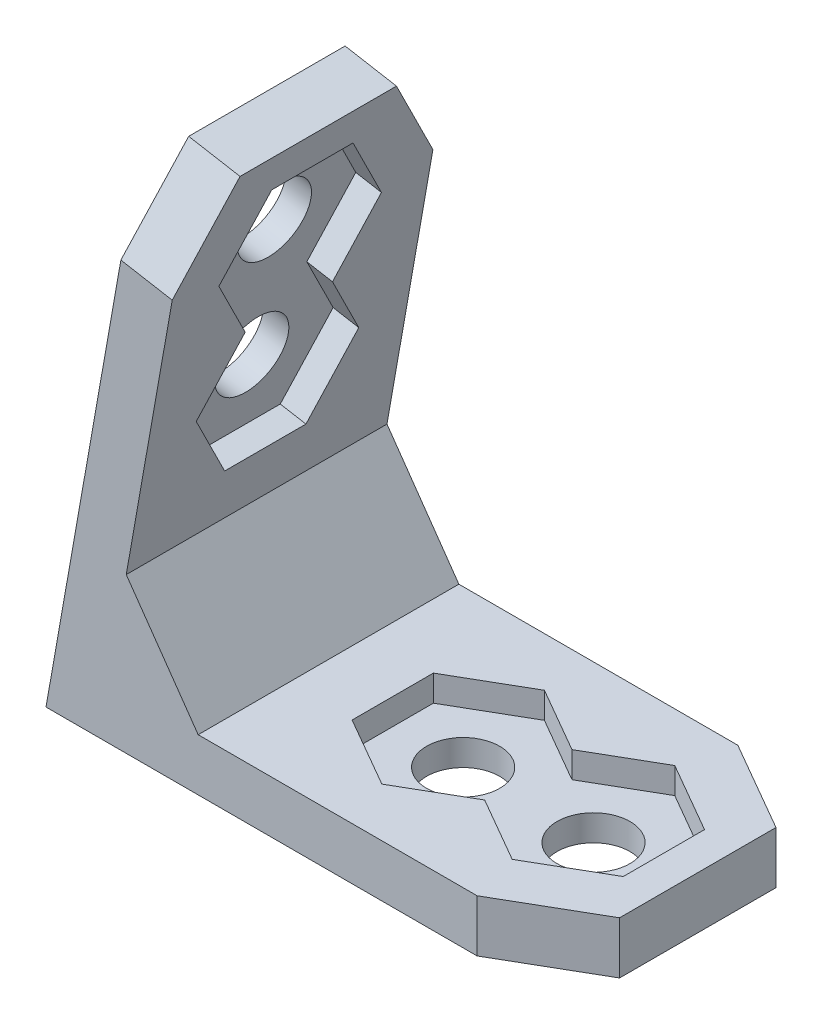
SolidWorks part; units mm, degrees
ref_plane "Front Plane" through (0, 0, 0) normal (0, 0, 1) x (1, 0, 0)
ref_plane "Top Plane" through (0, 0, 0) normal (0, 1, 0) x (1, 0, 0)
ref_plane "Right Plane" through (0, 0, 0) normal (1, 0, 0) x (0, 0, -1)
sketch "Sketch1" plane through (0, 0, 0) normal (0, 1, 0) x (1, 0, 0)
  line L1 (0, 0) -> (25.4, 0)
  line L2 (0, 0) -> (0, -12.7)
  line L3 (0, -12.7) -> (25.4, -12.7)
  line L4 (25.4, 0) -> (25.4, -12.7)
  dimension "D1" = 25.4
  dimension "D2" = 12.7
extrude "Boss-Extrude1" add sketch "Sketch1" along normal blind 2.54 contours L1 L4 L3 L2
sketch "Sketch2" plane through (0, 2.54, 0) normal (0, 1, 0) x (1, 0, 0)
  line L0 (0, -6.35) -> (25.4, -6.35) construction
  line L1 (0, 0) -> (0, -12.7) construction
  line L2 (25.4, 0) -> (25.4, -12.7) construction
  circle A0 centre (13.97, -6.35) radius 1.778
  circle A1 centre (20.32, -6.35) radius 1.778
  point P10 (11.807, -6.35)
  dimension "D2" = 3.556
  dimension "D1" = 6.35
  dimension "D3" = 5.08
extrude "Cut-Extrude1" cut sketch "Sketch2" against normal through all contours A1 L0 | L0 A1 | L0 A0 | A0 L0 region at (13.97, 2.54, 5.5954) region at (20.32, 2.54, 5.5954) region at (20.32, 2.54, 7.1046) region at (13.97, 2.54, 7.1046)
sketch "Sketch4" plane through (0, 2.54, 0) normal (0, 1, 0) x (1, 0, 0)
  line L1 (13.97, -2.3905) -> (10.541, -4.3703)
  line L2 (10.541, -4.3703) -> (10.541, -8.3297)
  line L3 (10.541, -8.3297) -> (13.97, -10.3095)
  line L4 (13.97, -10.3095) -> (17.399, -8.3297)
  line L5 (17.399, -8.3297) -> (17.399, -4.3703)
  line L6 (17.399, -4.3703) -> (13.97, -2.3905)
  line L7 (20.32, -2.3905) -> (16.891, -4.3703)
  line L8 (16.891, -4.3703) -> (16.891, -8.3297)
  line L9 (16.891, -8.3297) -> (20.32, -10.3095)
  line L10 (20.32, -10.3095) -> (23.749, -8.3297)
  line L11 (23.749, -8.3297) -> (23.749, -4.3703)
  line L12 (23.749, -4.3703) -> (20.32, -2.3905)
  circle A0 centre (13.97, -6.35) radius 3.429 construction
  circle A1 centre (20.32, -6.35) radius 3.429 construction
  point P10 (0, 0)
  point P19 (7.62, -2.8009)
  point P20 (13.97, -2.9841)
  circle M13 centre (20.32, -6.35) radius 1.778
  circle M14 centre (13.97, -6.35) radius 1.778
  dimension "D1" = 6.858
chamfer "Chamfer1" distance 2.54 angle 50 1 edges at (0, 2.54, 6.35) first distance on face at (0, 1.27, 6.35)
extrude "Cut-Extrude2" cut sketch "Sketch4" against normal blind 1.27 contours L9 L8 L7 L6 L1 L2 L3 L4 M14 | L11 L12 L7 L6 L5 L4 L9 L10 M13 | L8 L9 L4 L5 L6 L7 region at (15.5059, 2.54, 3.3964) region at (18.7841, 2.54, 3.3964) region at (17.145, 2.54, 6.35)
chamfer "Chamfer3" distance 2.54 angle 60 2 edges at (25.4, 1.27, 0) (25.4, 1.27, 12.7) first distance on face at (25.4, 1.27, 6.35)
mirror "Mirror1" about plane through (3.0271, 2.54, 0) normal (-0.6428, 0.766, 0) of bodies 105 103
chamfer "Chamfer2" distance 5.08 angle 45 1 edges at (3.0271, 2.54, 6.35) first distance on face at (5.4786, 16.4435, 6.35)
equation "\"D1@Chamfer1\"=\"D1@Boss-Extrude1\""
